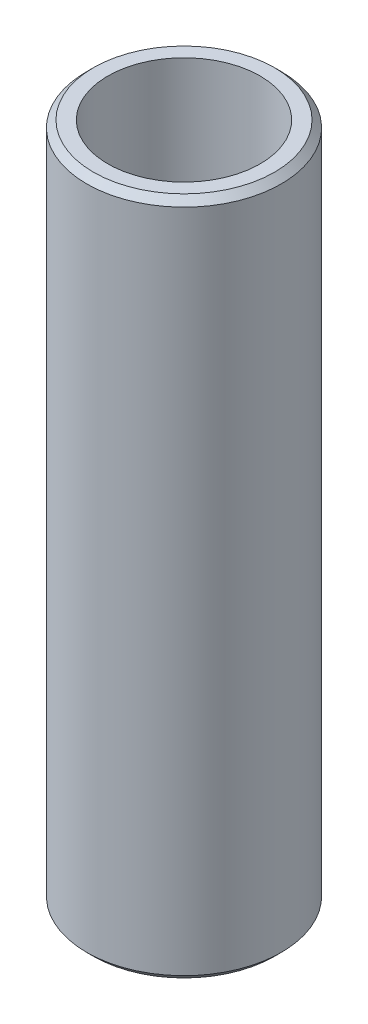
SolidWorks part; units mm, degrees
ref_plane "Front Plane" through (0, 0, 0) normal (0, 0, 1) x (1, 0, 0)
ref_plane "Top Plane" through (0, 0, 0) normal (0, 1, 0) x (1, 0, 0)
ref_plane "Right Plane" through (0, 0, 0) normal (1, 0, 0) x (0, 0, -1)
sketch "Sketch1" plane through (0, 0, 0) normal (0, 1, 0) x (1, 0, 0)
  circle A0 centre (0, 0) radius 32.5
  dimension "SHAFT_OD" = 65
extrude "Boss-Extrude1" add sketch "Sketch1" along normal blind 226.802
sketch "Sketch2" plane through (0, 0, 0) normal (0, 1, 0) x (1, 0, 0)
  circle A0 centre (0, 0) radius 25.4406
  dimension "BORE_D" = 50.8812
extrude "Cut-Extrude1" cut sketch "Sketch2" along normal through all
chamfer "Chamfer1" distance 2.2563 angle 45 2 edges at (0, 226.802, 32.5) (0, 0, 32.5)
